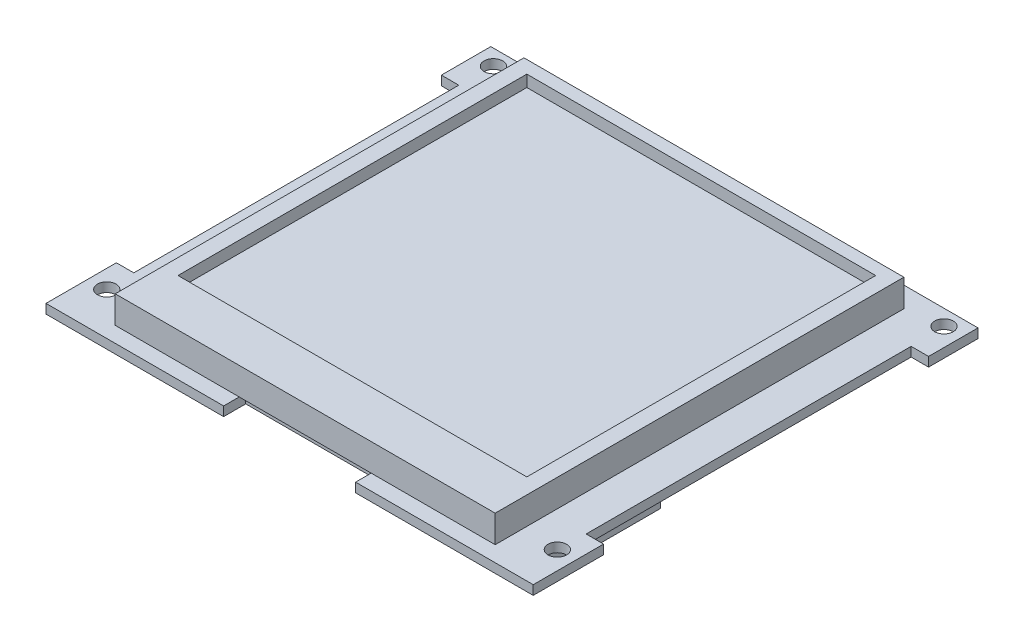
SolidWorks part; units mm, degrees
other "显示屏"
other "PCB"
ref_plane "前视基准面" through (0, 0, 0) normal (0, 0, 1) x (1, 0, 0)
ref_plane "上视基准面" through (0, 0, 0) normal (0, 1, 0) x (1, 0, 0)
ref_plane "右视基准面" through (0, 0, 0) normal (1, 0, 0) x (0, 0, -1)
other "Configuration Table"
sketch "草图1" plane through (0, 0, 0) normal (0, 1, 0) x (1, 0, 0)
  line L1 (-30, 70.8) -> (30, 70.8)
  line L2 (-30, 70.8) -> (-30, 10.8)
  line L3 (-30, 10.8) -> (30, 10.8)
  line L4 (30, 70.8) -> (30, 10.8)
  line L5 (-32.675, 72.98) -> (32.675, 72.98)
  line L6 (-32.675, 72.98) -> (-32.675, 2.68)
  line L7 (-32.675, 2.68) -> (32.675, 2.68)
  line L8 (32.675, 72.98) -> (32.675, 2.68)
  line L9 (-38.75, 73.8) -> (38.75, 73.8) construction
  line L10 (-38.75, 73.8) -> (-38.75, 7.3) construction
  line L11 (-38.75, 7.3) -> (38.75, 7.3) construction
  line L12 (38.75, 73.8) -> (38.75, 7.3) construction
  line L28 (-41.9, 76.5) -> (-41.9, 68)
  line L29 (-41.9, 68) -> (-38.9, 68)
  line L30 (-38.9, 68) -> (-38.9, 12.1)
  line L31 (-38.9, 12.1) -> (-41.9, 12.1)
  line L32 (-41.9, 12.1) -> (-41.9, 0)
  line L33 (0, 76.5) -> (0, 3.8) construction
  line L34 (-41.9, 0) -> (-11.35, 0)
  line L35 (-11.35, 0) -> (-11.35, 3.8)
  line L36 (11.35, 0) -> (11.35, 3.8)
  line L37 (41.9, 0) -> (11.35, 0)
  line L38 (41.9, 12.1) -> (41.9, 0)
  line L39 (38.9, 12.1) -> (41.9, 12.1)
  line L40 (38.9, 68) -> (38.9, 12.1)
  line L41 (41.9, 68) -> (38.9, 68)
  line L42 (41.9, 76.5) -> (41.9, 68)
  line L43 (-41.9, 76.5) -> (41.9, 76.5)
  line L44 (-11.35, 3.8) -> (11.35, 3.8)
  circle A0 centre (-38.75, 73.8) radius 1.6
  circle A1 centre (38.75, 73.8) radius 1.6
  circle A2 centre (38.75, 7.3) radius 1.6
  circle A3 centre (-38.75, 7.3) radius 1.6
  point P6 (0, 73.8)
  point P11 (0, 70.8)
  point P12 (0, 72.98)
  point P39 (0, 76.5)
  point P40 (0, 3.8)
  dimension "D7" = 3.2
  dimension "D1" = 60
  dimension "D2" = 60
  dimension "D3" = 65.35
  dimension "D4" = 70.3
  dimension "D5" = 77.5
  dimension "D6" = 66.5
  dimension "D8" = 83.8
  dimension "D9" = 8.5
  dimension "D10" = 55.9
  dimension "D11" = 12.1
  dimension "D12" = 3
  dimension "D13" = 22.7
  dimension "D14" = 3.8
  dimension "D15" = 2.68
  dimension "D16" = 7.3
  dimension "D17" = 10.8
extrude "凸台-拉伸1" add sketch "草图1" along normal blind 1.6 contours L34 L35 L44 L36 L37 L38 L39 L40 L41 L42 L43 L28 L29 L30 L31 L32 | A3 | A0 | A1 | A2
extrude "凸台-拉伸2" add sketch "草图1<3>" along normal blind 4.7 from surface separate body contours L6 L7 L8 L5 starting at face at (38.75, 1.6, -72.2)
sketch "草图1<3>" plane through (0, 0, 0) normal (0, 1, 0) x (1, 0, 0) same geometry as "草图1"
extrude "切除-拉伸1" cut sketch "草图1<4>" against normal blind 2 from surface contours L2 L3 L4 L1 starting at face at (0, 6.3, -37.83)
sketch "草图1<4>" plane through (0, 0, 0) normal (0, 1, 0) x (1, 0, 0) same geometry as "草图1"
sketch "草图2" plane through (0, 0, 0) normal (0, -1, 0) x (1, 0, 0)
  line L0 (41.9, -12.1) -> (41.9, 0) construction
  line L1 (30.9, -32.91) -> (25.9, -32.91)
  line L2 (30.9, -32.91) -> (30.9, -9.65)
  line L3 (30.9, -9.65) -> (25.9, -9.65)
  line L4 (25.9, -32.91) -> (25.9, -9.65)
  line L5 (32.05, -13.96) -> (32.05, -13.36)
  line L6 (28.4, -32.91) -> (28.4, -9.65) construction
  line L7 (32.05, -11.42) -> (30.9, -11.42)
  line L8 (32.05, -11.42) -> (32.05, -10.82)
  line L9 (32.05, -10.82) -> (30.9, -10.82)
  line L10 (30.9, -11.42) -> (30.9, -10.82)
  line L11 (32.05, -13.96) -> (30.9, -13.96)
  line L12 (30.9, -13.96) -> (30.9, -13.36)
  line L13 (32.05, -13.36) -> (30.9, -13.36)
  line L14 (32.05, -16.5) -> (32.05, -15.9)
  line L15 (32.05, -16.5) -> (30.9, -16.5)
  line L16 (30.9, -16.5) -> (30.9, -15.9)
  line L17 (32.05, -15.9) -> (30.9, -15.9)
  line L18 (32.05, -19.04) -> (32.05, -18.44)
  line L19 (32.05, -19.04) -> (30.9, -19.04)
  line L20 (30.9, -19.04) -> (30.9, -18.44)
  line L21 (32.05, -18.44) -> (30.9, -18.44)
  line L22 (32.05, -21.58) -> (32.05, -20.98)
  line L23 (32.05, -21.58) -> (30.9, -21.58)
  line L24 (30.9, -21.58) -> (30.9, -20.98)
  line L25 (32.05, -20.98) -> (30.9, -20.98)
  line L26 (32.05, -24.12) -> (32.05, -23.52)
  line L27 (32.05, -24.12) -> (30.9, -24.12)
  line L28 (30.9, -24.12) -> (30.9, -23.52)
  line L29 (32.05, -23.52) -> (30.9, -23.52)
  line L30 (32.05, -26.66) -> (32.05, -26.06)
  line L31 (32.05, -26.66) -> (30.9, -26.66)
  line L32 (30.9, -26.66) -> (30.9, -26.06)
  line L33 (32.05, -26.06) -> (30.9, -26.06)
  line L34 (32.05, -29.2) -> (32.05, -28.6)
  line L35 (32.05, -29.2) -> (30.9, -29.2)
  line L36 (30.9, -29.2) -> (30.9, -28.6)
  line L37 (32.05, -28.6) -> (30.9, -28.6)
  line L38 (32.05, -31.74) -> (32.05, -31.14)
  line L39 (32.05, -31.74) -> (30.9, -31.74)
  line L40 (30.9, -31.74) -> (30.9, -31.14)
  line L41 (32.05, -31.14) -> (30.9, -31.14)
  line L42 (32.05, -11.42) -> (32.05, -13.96) construction
  line L43 (24.75, -31.74) -> (25.9, -31.74)
  line L44 (25.9, -31.74) -> (25.9, -31.14)
  line L45 (24.75, -31.14) -> (25.9, -31.14)
  line L46 (24.75, -31.74) -> (24.75, -31.14)
  line L47 (24.75, -29.2) -> (25.9, -29.2)
  line L48 (25.9, -29.2) -> (25.9, -28.6)
  line L49 (24.75, -28.6) -> (25.9, -28.6)
  line L50 (24.75, -29.2) -> (24.75, -28.6)
  line L51 (24.75, -26.66) -> (25.9, -26.66)
  line L52 (25.9, -26.66) -> (25.9, -26.06)
  line L53 (24.75, -26.06) -> (25.9, -26.06)
  line L54 (24.75, -26.66) -> (24.75, -26.06)
  line L55 (24.75, -24.12) -> (25.9, -24.12)
  line L56 (25.9, -24.12) -> (25.9, -23.52)
  line L57 (24.75, -23.52) -> (25.9, -23.52)
  line L58 (24.75, -24.12) -> (24.75, -23.52)
  line L59 (24.75, -21.58) -> (25.9, -21.58)
  line L60 (25.9, -21.58) -> (25.9, -20.98)
  line L61 (24.75, -20.98) -> (25.9, -20.98)
  line L62 (24.75, -21.58) -> (24.75, -20.98)
  line L63 (24.75, -19.04) -> (25.9, -19.04)
  line L64 (25.9, -19.04) -> (25.9, -18.44)
  line L65 (24.75, -18.44) -> (25.9, -18.44)
  line L66 (24.75, -19.04) -> (24.75, -18.44)
  line L67 (24.75, -16.5) -> (25.9, -16.5)
  line L68 (25.9, -16.5) -> (25.9, -15.9)
  line L69 (24.75, -15.9) -> (25.9, -15.9)
  line L70 (24.75, -16.5) -> (24.75, -15.9)
  line L71 (24.75, -13.96) -> (25.9, -13.96)
  line L72 (25.9, -13.96) -> (25.9, -13.36)
  line L73 (24.75, -13.36) -> (25.9, -13.36)
  line L74 (24.75, -13.96) -> (24.75, -13.36)
  line L75 (24.75, -10.82) -> (25.9, -10.82)
  line L76 (25.9, -11.42) -> (25.9, -10.82)
  line L77 (24.75, -11.42) -> (25.9, -11.42)
  line L78 (24.75, -11.42) -> (24.75, -10.82)
  line L79 (24.75, -10.82) -> (24.75, -9.65) construction
  line L80 (24.75, -31.74) -> (24.75, -32.91) construction
  line L81 (41.9, 0) -> (11.35, 0) construction
  line L82 (30.42, -11.87) -> (28.92, -11.87)
  line L83 (26.38, -10.37) -> (27.88, -10.37)
  line L84 (26.38, -10.37) -> (26.38, -11.87)
  line L85 (26.38, -11.87) -> (27.88, -11.87)
  line L86 (27.88, -10.37) -> (27.88, -11.87)
  line L87 (28.92, -10.37) -> (28.92, -11.87)
  line L88 (30.42, -10.37) -> (28.92, -10.37)
  line L89 (30.42, -10.37) -> (30.42, -11.87)
  line L90 (26.38, -12.91) -> (26.38, -14.41)
  line L91 (26.38, -12.91) -> (27.88, -12.91)
  line L92 (27.88, -12.91) -> (27.88, -14.41)
  line L93 (26.38, -14.41) -> (27.88, -14.41)
  line L94 (30.42, -14.41) -> (28.92, -14.41)
  line L95 (28.92, -12.91) -> (28.92, -14.41)
  line L96 (30.42, -12.91) -> (28.92, -12.91)
  line L97 (30.42, -12.91) -> (30.42, -14.41)
  line L98 (26.38, -15.45) -> (26.38, -16.95)
  line L99 (26.38, -15.45) -> (27.88, -15.45)
  line L100 (27.88, -15.45) -> (27.88, -16.95)
  line L101 (26.38, -16.95) -> (27.88, -16.95)
  line L102 (30.42, -16.95) -> (28.92, -16.95)
  line L103 (28.92, -15.45) -> (28.92, -16.95)
  line L104 (30.42, -15.45) -> (28.92, -15.45)
  line L105 (30.42, -15.45) -> (30.42, -16.95)
  line L106 (26.38, -17.99) -> (26.38, -19.49)
  line L107 (26.38, -17.99) -> (27.88, -17.99)
  line L108 (27.88, -17.99) -> (27.88, -19.49)
  line L109 (26.38, -19.49) -> (27.88, -19.49)
  line L110 (30.42, -19.49) -> (28.92, -19.49)
  line L111 (28.92, -17.99) -> (28.92, -19.49)
  line L112 (30.42, -17.99) -> (28.92, -17.99)
  line L113 (30.42, -17.99) -> (30.42, -19.49)
  line L114 (26.38, -20.53) -> (26.38, -22.03)
  line L115 (26.38, -20.53) -> (27.88, -20.53)
  line L116 (27.88, -20.53) -> (27.88, -22.03)
  line L117 (26.38, -22.03) -> (27.88, -22.03)
  line L118 (30.42, -22.03) -> (28.92, -22.03)
  line L119 (28.92, -20.53) -> (28.92, -22.03)
  line L120 (30.42, -20.53) -> (28.92, -20.53)
  line L121 (30.42, -20.53) -> (30.42, -22.03)
  line L122 (26.38, -23.07) -> (26.38, -24.57)
  line L123 (26.38, -23.07) -> (27.88, -23.07)
  line L124 (27.88, -23.07) -> (27.88, -24.57)
  line L125 (26.38, -24.57) -> (27.88, -24.57)
  line L126 (30.42, -24.57) -> (28.92, -24.57)
  line L127 (28.92, -23.07) -> (28.92, -24.57)
  line L128 (30.42, -23.07) -> (28.92, -23.07)
  line L129 (30.42, -23.07) -> (30.42, -24.57)
  line L130 (26.38, -25.61) -> (26.38, -27.11)
  line L131 (26.38, -25.61) -> (27.88, -25.61)
  line L132 (27.88, -25.61) -> (27.88, -27.11)
  line L133 (26.38, -27.11) -> (27.88, -27.11)
  line L134 (30.42, -27.11) -> (28.92, -27.11)
  line L135 (28.92, -25.61) -> (28.92, -27.11)
  line L136 (30.42, -25.61) -> (28.92, -25.61)
  line L137 (30.42, -25.61) -> (30.42, -27.11)
  line L138 (26.38, -28.15) -> (26.38, -29.65)
  line L139 (26.38, -28.15) -> (27.88, -28.15)
  line L140 (27.88, -28.15) -> (27.88, -29.65)
  line L141 (26.38, -29.65) -> (27.88, -29.65)
  line L142 (30.42, -29.65) -> (28.92, -29.65)
  line L143 (28.92, -28.15) -> (28.92, -29.65)
  line L144 (30.42, -28.15) -> (28.92, -28.15)
  line L145 (30.42, -28.15) -> (30.42, -29.65)
  line L146 (26.38, -30.69) -> (26.38, -32.19)
  line L147 (26.38, -30.69) -> (27.88, -30.69)
  line L148 (27.88, -30.69) -> (27.88, -32.19)
  line L149 (26.38, -32.19) -> (27.88, -32.19)
  line L150 (30.42, -32.19) -> (28.92, -32.19)
  line L151 (28.92, -30.69) -> (28.92, -32.19)
  line L152 (30.42, -30.69) -> (28.92, -30.69)
  line L153 (30.42, -30.69) -> (30.42, -32.19)
  line L154 (26.38, -10.37) -> (26.38, -12.91) construction
  line L155 (41.9, 0) -> (11.35, 0) construction
  point P91 (32.05, -11.12)
  point P96 (24.75, -11.12)
  point P97 (26.38, -11.12)
  point P164 (27.13, -10.37)
  point P165 (29.67, -10.37)
  dimension "D1" = 23.26
  dimension "D2" = 5
  dimension "D3" = 13.5
  dimension "D4" = 0.6
  dimension "D6" = 2.54
  dimension "D7" = 7.3
  dimension "D8" = 11.12
  dimension "D10" = 2.54
  dimension "D11" = 2.54
  dimension "D12" = 1.5
  dimension "D13" = 9.65
  dimension "D5" = 9
  dimension "D9" = 9
extrude "凸台-拉伸3" add sketch "草图2" along normal blind 9 separate body contours L3 L4 L1 L2
extrude "凸台-拉伸4" add sketch "草图2<3>" along normal blind 0.5 contours L9 L10 L7 L8 | L13 L12 L11 L5 | L17 L16 L15 L14 | L41 L40 L39 L38 | L37 L36 L35 L34 | L33 L32 L31 L30 | L27 L28 L29 L26 | L23 L24 L25 L22 | L21 L20 L19 L18 | L45 L44 L43 L46 | L49 L48 L47 L50 | L53 L52 L51 L54 | L57 L56 L55 L58 | L61 L60 L59 L62 | L65 L64 L63 L66 | L67 L68 L69 L70 | L71 L72 L73 L74 | L75 L76 L77 L78
sketch "草图2<3>" plane through (0, 0, 0) normal (0, -1, 0) x (1, 0, 0) same geometry as "草图2"
extrude "切除-拉伸2" cut sketch "草图2<4>" against normal blind 5 from surface contours L151 L150 L153 L152 | L148 L149 L146 L147 | L143 L142 L145 L144 | L140 L141 L138 L139 | L135 L134 L137 L136 | L132 L133 L130 L131 | L127 L126 L129 L128 | L124 L125 L122 L123 | L119 L118 L121 L120 | L116 L117 L114 L115 | L111 L110 L113 L112 | L108 L109 L106 L107 | L103 L102 L105 L104 | L100 L101 L98 L99 | L95 L94 L97 L96 | L92 L93 L90 L91 | L87 L82 L89 L88 | L86 L85 L84 L83 starting at face at (28.4, -9, -21.28)
sketch "草图2<4>" plane through (0, 0, 0) normal (0, -1, 0) x (1, 0, 0) same geometry as "草图2"
